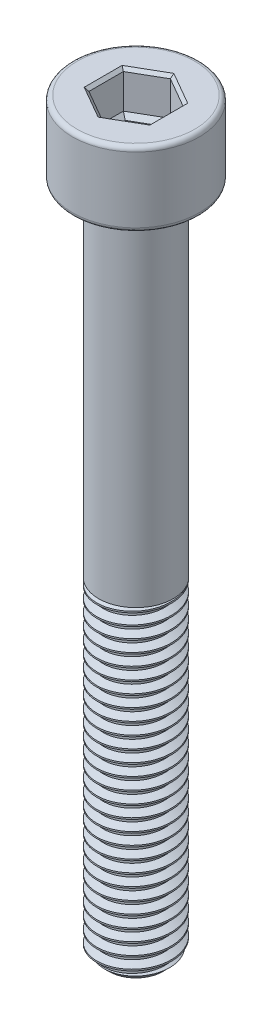
SolidWorks part; units mm, degrees
material "AISI Type A2 Tool Steel"
ref_plane "Front Plane" through (0, 0, 0) normal (0, 0, 1) x (1, 0, 0)
ref_plane "Top Plane" through (0, 0, 0) normal (0, 1, 0) x (1, 0, 0)
ref_plane "Right Plane" through (0, 0, 0) normal (1, 0, 0) x (0, 0, -1)
sketch "Sketch1" plane through (0, 0, 0) normal (0, 1, 0) x (1, 0, 0)
  circle A0 centre (0, 0) radius 2.5
  dimension "D1" = 5
extrude "Boss-Extrude1" add sketch "Sketch1" along normal blind 22
thread "Thread1" pitch 0.8 method cut profile "Thread Profile1" start angle 0, offset 1, length 0, pitch 0.8, diameter 5
ref_plane "Plane1" through (-2.5, 23, 0) normal (0, 0, 1) x (-1, 0, 0)
sketch "Thread Profile1" plane through (-2.5, 23, 0) normal (0, 0, 1) x (-1, 0, 0)
  line L0 (0, 0) -> (0, 0.8) construction
  line L11 (0, 0) -> (0, 0.7)
  line L12 (0, 0.7) -> (-0.433, 0.45)
  line L13 (-0.433, 0.45) -> (-0.433, 0.25)
  line L15 (-0.433, 0.25) -> (0, 0)
  line L17 (-0.433, 0.35) -> (0, 0.35) construction
  point P2 (0, 0)
  dimension "Pitch" = 0.8
  dimension "Profile_Angle" = 60
  dimension "Profile_Land" = 0.2
  dimension "Profile_Height" = 0.433
sketch "Sketch2" plane through (0, 22, 0) normal (0, 1, 0) x (1, 0, 0)
  circle A0 centre (0, 0) radius 2.5
  dimension "D1" = 5
extrude "Boss-Extrude2" add sketch "Sketch2" along normal blind 23
sketch "Sketch3" plane through (0, 45, 0) normal (0, 1, 0) x (1, 0, 0)
  circle A0 centre (0, 0) radius 4.25
  dimension "D1" = 8.5
extrude "Boss-Extrude3" add sketch "Sketch3" along normal blind 5
fillet "Fillet1" radius 0.3 2 edges at (0, 45, 4.25) (0, 50, 4.25)
sketch "Sketch4" plane through (0, 0, 0) normal (0, 0, 1) x (1, 0, 0)
  line L0 (0, 0) -> (0, 0.4416) construction
  line L1 (0, 0) -> (2.51, 0) construction
  line L2 (2.51, 0) -> (2.51, 0.7)
  line L3 (2.51, 0.7) -> (1.81, 0)
  line L4 (1.81, 0) -> (2.51, 0)
  dimension "D1" = 0.7
  dimension "D2" = 45
  dimension "D3" = 2.51
revolve "Cut-Revolve1" cut sketch "Sketch4" angle 360 about L0
sketch "Sketch5" plane through (0, 50, 0) normal (0, 1, 0) x (1, 0, 0)
  line L1 (0, 2.3094) -> (-2, 1.1547)
  line L2 (-2, 1.1547) -> (-2, -1.1547)
  line L3 (-2, -1.1547) -> (0, -2.3094)
  line L4 (0, -2.3094) -> (2, -1.1547)
  line L5 (2, -1.1547) -> (2, 1.1547)
  line L6 (2, 1.1547) -> (0, 2.3094)
  circle A0 centre (0, 0) radius 2 construction
  dimension "D1" = 4
extrude "Cut-Extrude1" cut sketch "Sketch5" against normal blind 2.5
chamfer "Chamfer1" distance 0.2 angle 45 6 edges at (-1, 50, 1.7321) (1, 50, 1.7321) (2, 50, 0) (1, 50, -1.7321) (-1, 50, -1.7321) (-2, 50, 0)
sketch "Sketch6" plane through (0, 47.5, 0) normal (0, 1, 0) x (1, 0, 0)
  line L1 (0, 2.3094) -> (-2, 1.1547)
  line L2 (-2, 1.1547) -> (-2, -1.1547)
  line L3 (-2, -1.1547) -> (0, -2.3094)
  line L4 (0, -2.3094) -> (2, -1.1547)
  line L5 (2, -1.1547) -> (2, 1.1547)
  line L6 (2, 1.1547) -> (0, 2.3094)
  circle A0 centre (0, 0) radius 2 construction
extrude "Cut-Extrude2" cut sketch "Sketch6" against normal blind 0.3 draft 45
